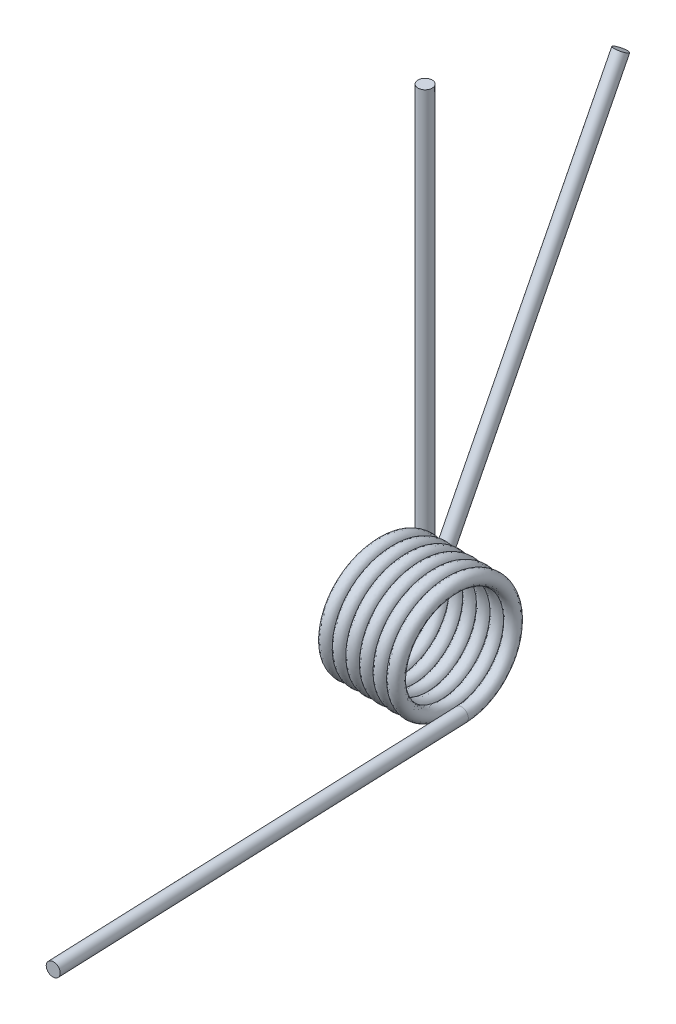
SolidWorks part; units mm, degrees
ref_plane "Front" through (0, 0, 0) normal (0, 0, 1) x (1, 0, 0)
ref_plane "Top" through (0, 0, 0) normal (0, 1, 0) x (1, 0, 0)
ref_plane "Right" through (0, 0, 0) normal (1, 0, 0) x (0, 0, -1)
sketch "Sketch1" plane through (0, 0, 0) normal (1, 0, 0) x (0, 0, -1)
  line L0 (0, -8.6487) -> (0, -11.0617) construction
  line L1 (9.5797, -5.5309) -> (47.6797, 60.4603) construction
  line L2 (0, -11.0617) -> (-76.2, -11.0617) construction
  line L3 (0, 0) -> (11.0617, 0) construction
  line L4 (0, 0) -> (9.5797, -5.5309) construction
  line L5 (-76.2, -11.0617) -> (-76.2, -8.6487) construction
  line L6 (-76.2, -8.6487) -> (0, -8.6487) construction
  line L7 (47.6797, 60.4603) -> (45.59, 61.6668) construction
  line L8 (45.59, 61.6668) -> (7.49, -4.3244) construction
  circle A0 centre (0, 0) radius 11.0617 construction
  circle A1 centre (0, 0) radius 7.9375 construction
  circle A2 centre (0, 0) radius 9.8552 construction
  point P7 (0, -9.8552)
  point P10 (0, 11.0617)
  dimension "OD" = 22.1234
  dimension "For Shaft Diameter" = 15.875
  dimension "Wire Diameter" = 2.413
  dimension "Leg Length" = 76.2
  dimension "Deflection Angle" = 120
sketch "Sketch2" plane through (0, 0, 0) normal (1, 0, 0) x (0, 0, -1)
  circle A0 centre (0, 0) radius 9.8552 construction
  circle A2 centre (0, 0) radius 9.8552
curve "Helix/Spiral1" pitch 2.4384 height 15.0368 radius 9.8552 left hand yes centre (0, 0, 0) axis (-1, 0, 0) start towards (0, 0, -1)
ref_plane "Plane1" through (0, -9.8552, 0) normal (-0.0393, 0, -0.9992) x (0.999, -0.0232, -0.0393)
sketch "Sketch3" plane through (0, -9.8552, 0) normal (-0.0393, 0, -0.9992) x (0.999, -0.0232, -0.0393)
  circle A0 centre (0, 0) radius 1.2065
  dimension "D1" = 2.413
sweep "Sweep1" add profiles "Sketch3" path "Helix/Spiral1"
sketch "Sketch4" plane through (0, 0, 0) normal (0.0393, 0, 0.9992) x (-0.999, 0.0232, 0.0393)
  circle A1 centre (-0.229, 9.8525) radius 1.2065
  circle A2 centre (-0.229, 9.8525) radius 1.2065
  dimension "D1" = 0
extrude "Extrude1" add sketch "Sketch4" along normal blind 76.2
sketch "Sketch5" plane through (-0.0233, 0.512, -0.2956) normal (-0.0393, 0.8654, -0.4996) x (0.9992, 0.0341, -0.0196)
  circle A1 centre (-15.0255, 9.8547) radius 1.2065
  circle A2 centre (-15.0255, 9.8547) radius 1.2065
  dimension "D1" = 0
extrude "Extrude2" add sketch "Sketch5" along normal blind 76.2
sketch "Sketch6" plane through (0, 0, 0) normal (1, 0, 0) x (0, 0, -1)
  circle A2 centre (0, 0) radius 8.6487 construction
sketch "Sketch7" plane through (0, 0, 0) normal (0, 1, 0) x (1, 0, 0)
  circle A0 centre (-15.0368, 8.5349) radius 1.27
  dimension "D1" = 2.54
extrude "Boss-Extrude1" add sketch "Sketch7" along normal blind 76.2
sketch "Sketch8" plane through (0, 0, 0) normal (1, 0, 0) x (0, 0, -1)
  line L0 (0, 0) -> (-70.1217, 0)
  circle A0 centre (0, 0) radius 10.9789
equation "\"D4@Helix/Spiral1\" = \"Wire Diameter@Sketch1\" + .001"
equation "\"D1@Sketch3\"=\"Wire Diameter@Sketch1\""
equation "\"D1@Extrude2\"=\"Leg Length@Sketch1\""
equation "\"Leg Length@Extrude1\"=\"Leg Length@Sketch1\""
